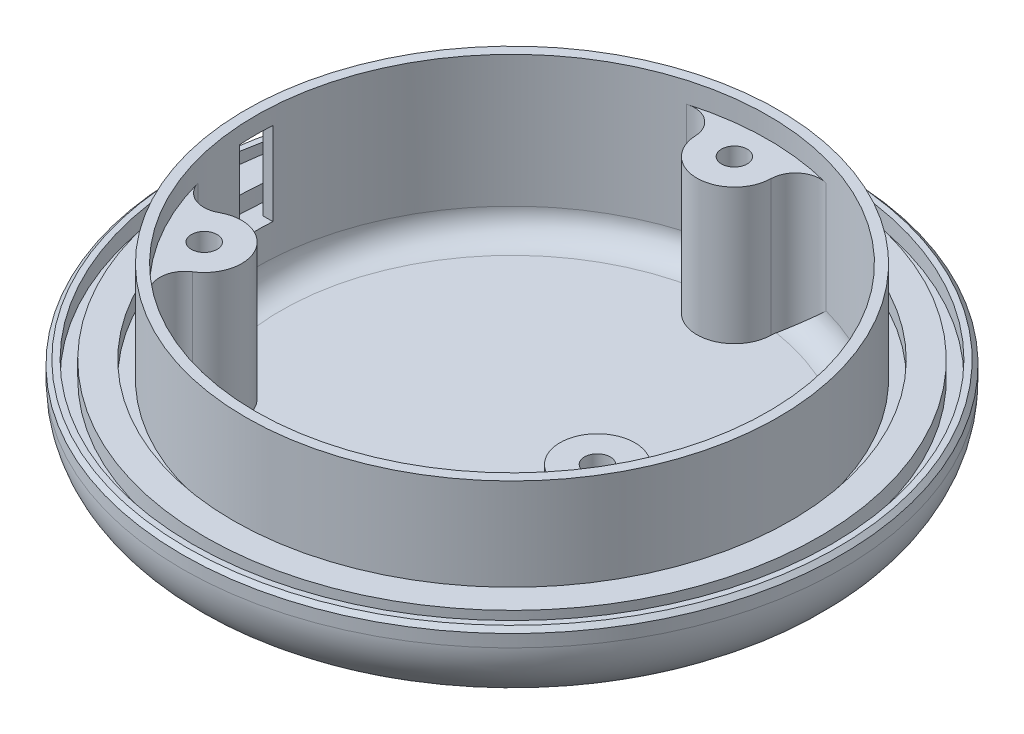
SolidWorks part; units mm, degrees
ref_plane "Plan de face" through (0, 0, 0) normal (0, 0, 1) x (1, 0, 0)
ref_plane "Plan de dessus" through (0, 0, 0) normal (0, 1, 0) x (1, 0, 0)
ref_plane "Plan de droite" through (0, 0, 0) normal (1, 0, 0) x (0, 0, -1)
sketch "Esquisse2" plane through (0, 0, 0) normal (0, 0, 1) x (1, 0, 0)
  line L0 (-39.6, 8) -> (-39.6, 10)
  line L1 (0, 0) -> (-32, 0)
  line L2 (-39.6, 10) -> (-38.4, 10)
  line L3 (-38.4, 10) -> (-38.4, 8)
  line L4 (0, 24.4124) -> (0, -18.1737) construction
  line L5 (0, 1.2) -> (-30.8, 1.2)
  line L7 (-32, 8) -> (-32, 20)
  line L8 (-32, 20) -> (-30.8, 20)
  line L9 (-30.8, 20) -> (-30.8, 1.2)
  line L10 (-32, 8) -> (-33.5, 8)
  line L11 (0, 0) -> (0, 1.2)
  line L12 (-38.4, 8) -> (-36.9, 8)
  line L13 (-36.9, 8) -> (-36.9, 10)
  line L17 (-36.9, 10) -> (-33.5, 10)
  line L18 (-33.5, 8) -> (-33.5, 10)
  arc A0 (-39.6, 8) -> (-32, 0) centre (-31.5895, 8) ccw
  circle A1 centre (-34.3, 4.5) radius 2.75
  dimension "D2" = 32
  dimension "D5" = 12
  dimension "D20" = 5.5
  dimension "D4" = 1.5
  dimension "D6" = 30.8
  dimension "D7" = 2
  dimension "D8" = 3.4
  dimension "D9" = 90
  dimension "D10" = 2
  dimension "D11" = 1.2
  dimension "D12" = 2
  dimension "D13" = 1.2
  dimension "D14" = 8
  dimension "D17" = 1.5
  dimension "D18" = 1.2
  dimension "D19" = 8
  dimension "D21" = 3.5
  dimension "D22" = 4.5
revolve "Révolution1" add sketch "Esquisse2" angle 360 about L4
sketch "Esquisse3" plane through (0, 0, 0) normal (1, 0, 0) x (0, 0, -1)
  line L0 (-39.6, 8) -> (39.6, 8) construction
  line L1 (2, 21.9768) -> (-2, 21.9768)
  line L2 (2, 21.9768) -> (2, 8)
  line L3 (2, 8) -> (-2, 8)
  line L4 (-2, 21.9768) -> (-2, 8)
  dimension "D1" = 2
  dimension "D2" = 4
extrude "Enlèv. mat.-Extru.1" cut sketch "Esquisse3" against normal blind 32
sketch "Esquisse4" plane through (0, 1.2, 0) normal (0, 1, 0) x (1, 0, 0)
  line L0 (4.2215, 26.9986) -> (4.2215, 30.6492)
  line L1 (-4.7785, 26.9986) -> (-4.7785, 30.5673)
  line L2 (21.2707, -17.1552) -> (24.4323, -18.9805)
  line L3 (25.7707, -9.361) -> (28.8614, -11.1454)
  line L4 (-25.4922, -9.8434) -> (-28.6538, -11.6687)
  line L5 (-20.9922, -17.6376) -> (-24.0828, -19.422)
  arc A0 (4.2215, 30.6492) -> (-4.7785, 30.5673) centre (0, 0) ccw
  circle A1 centre (-0.2785, 26.9986) radius 1.55
  arc A2 (24.4323, -18.9805) -> (28.8614, -11.1454) centre (0, 0) ccw
  arc A3 (-4.7785, 26.9986) -> (4.2215, 26.9986) centre (-0.2785, 26.9986) ccw
  circle A4 centre (23.5207, -13.2581) radius 1.55
  arc A5 (25.7707, -9.361) -> (21.2707, -17.1552) centre (23.5207, -13.2581) ccw
  arc A6 (-28.6538, -11.6687) -> (-24.0828, -19.422) centre (0, 0) ccw
  circle A7 centre (-23.2422, -13.7405) radius 1.55
  arc A8 (-20.9922, -17.6376) -> (-25.4922, -9.8434) centre (-23.2422, -13.7405) ccw
  circle A13 centre (23.5207, -13.2581) radius 1.55 [skipped]
  circle A14 centre (-23.2422, -13.7405) radius 1.55 [skipped]
  point P8 (0, 0)
  point P9 (0, 0)
  point P10 (0, 0)
  point P11 (0, 0)
  point P12 (0, 0)
  point P13 (0, 0)
  point P16 (0, 0)
  point P21 (0, 0)
  point P33 (0, 0)
  point P34 (0, 0)
  point P35 (0, 0)
  point P37 (0, 0)
  point P41 (0, 0)
  dimension "D1" = 3.1
  dimension "D3" = 3
  dimension "D4" = 3
  dimension "D5" = 4.5
  dimension "D2" = 27
extrude "Boss.-Extru.1" add sketch "Esquisse4" along normal blind 16.3
fillet "Congé1" radius 3 9 edges at (0.2815, 1.2, 30.7987) (26.5317, 1.2, -15.6432) (-26.8132, 1.2, -15.1555) (-28.5326, 9.35, 11.5988) (28.7399, 9.35, 11.0752) (24.3111, 9.35, 18.9106) (-4.7785, 9.35, -30.4271) (4.2215, 9.35, -30.5093) (-23.9613, 9.35, 19.3518)
chamfer "Chanfrein1" distance 0.5 angle 45 1 edges at (0, 10, 39.6)
sketch "Esquisse5" plane through (0, 20, 0) normal (0, 1, 0) x (1, 0, 0)
  circle A0 centre (0, 0) radius 32
  circle A1 centre (0, 0) radius 30.8
extrude "Boss.-Extru.2" add sketch "Esquisse5" against normal blind 2
